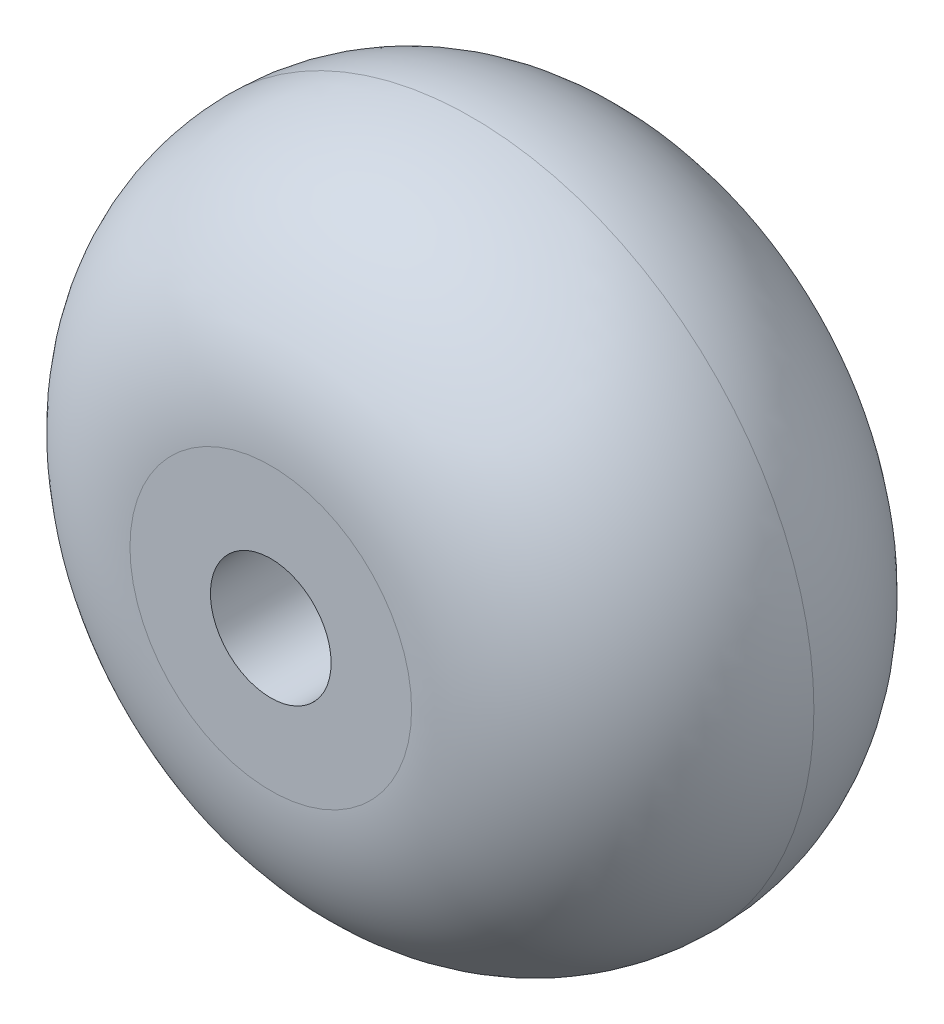
SolidWorks part; units mm, degrees
ref_plane "Plano frontal" through (0, 0, 0) normal (0, 0, 1) x (1, 0, 0)
ref_plane "Plano superior" through (0, 0, 0) normal (0, 1, 0) x (1, 0, 0)
ref_plane "Plano direito" through (0, 0, 0) normal (1, 0, 0) x (0, 0, -1)
sketch "Esboço1" plane through (0, 0, 0) normal (0, 0, 1) x (1, 0, 0)
  circle A0 centre (0, 0) radius 17
  circle A1 centre (0, 0) radius 3
  dimension "D2" = 6
  dimension "D3" = 34
extrude "Ressalto-extrusão1" add sketch "Esboço1" along normal blind 20
fillet "Filete1" radius 10 2 edges at (17, 0, 0) (17, 0, 20)
